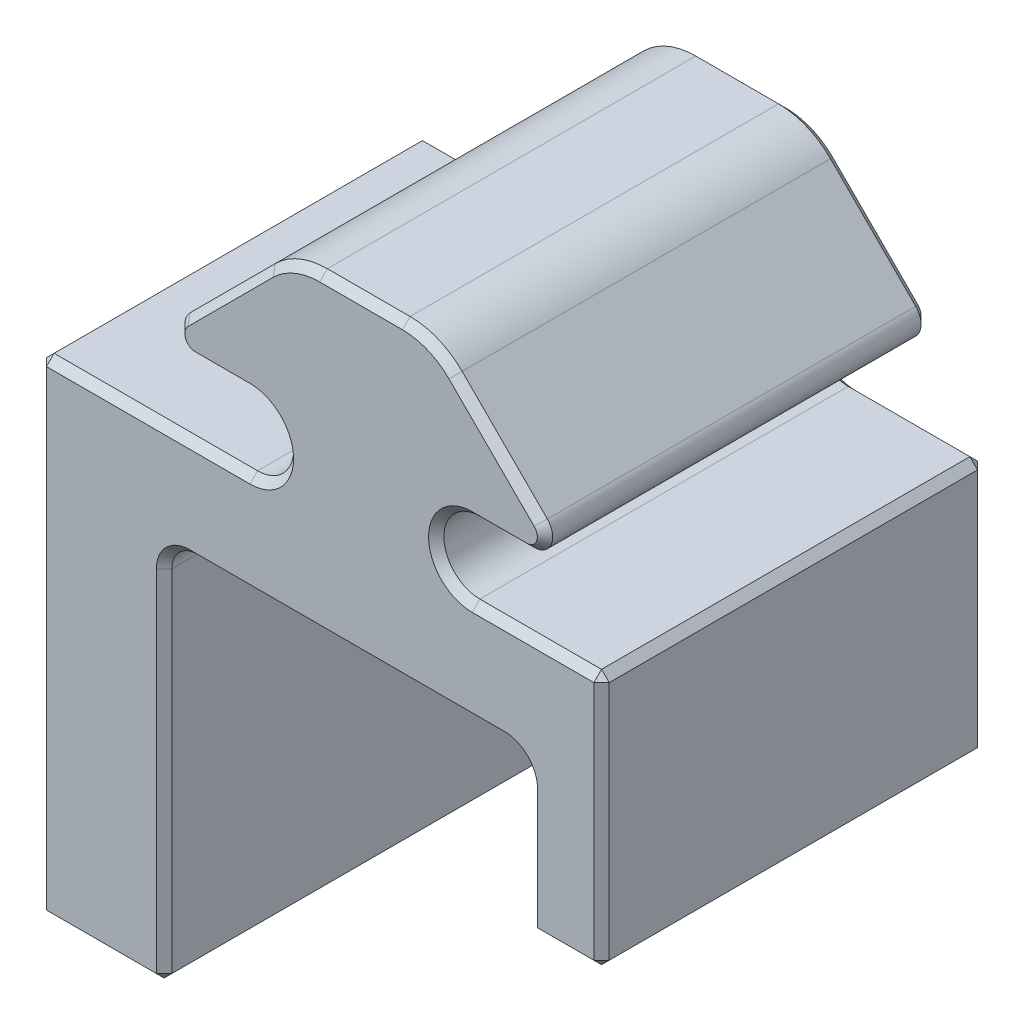
SolidWorks part; units mm, degrees
ref_plane "Front Plane" through (0, 0, 0) normal (0, 0, 1) x (1, 0, 0)
ref_plane "Top Plane" through (0, 0, 0) normal (0, 1, 0) x (1, 0, 0)
ref_plane "Right Plane" through (0, 0, 0) normal (1, 0, 0) x (0, 0, -1)
sketch "Sketch1" plane through (0, 0, 0) normal (0, 0, 1) x (1, 0, 0)
  line L0 (-5.3171, -3.1021) -> (-5.3171, -5.1021) construction
  line L1 (-5.3171, -5.1021) -> (5.3171, -5.1021) construction
  line L2 (5.3171, -5.1021) -> (5.3171, -3.1021) construction
  line L13 (-5.3171, -3.1021) -> (-4.3434, -3.1021) construction
  line L14 (-4.3434, -0.8923) -> (-6.4748, -0.8923) construction
  line L15 (-7.1932, 0.8421) -> (-3.8632, 4.1722) construction
  line L16 (-1.6181, 5.1021) -> (1.6181, 5.1021) construction
  line L17 (3.8632, 4.1722) -> (7.1932, 0.8421) construction
  line L18 (6.4748, -0.8923) -> (4.3434, -0.8923) construction
  line L19 (4.3434, -3.1021) -> (5.3171, -3.1021) construction
  line L20 (-5.0171, -3.4021) -> (-5.0171, -4.8021) construction
  line L21 (-5.0171, -4.8021) -> (5.0171, -4.8021) construction
  line L22 (5.0171, -4.8021) -> (5.0171, -3.4021) construction
  line L23 (4.3434, -3.4021) -> (5.0171, -3.4021)
  line L24 (6.4748, -0.5923) -> (4.3434, -0.5923)
  line L25 (3.651, 3.96) -> (6.9811, 0.63)
  line L26 (-1.6181, 4.8021) -> (1.6181, 4.8021)
  line L27 (-6.9811, 0.63) -> (-3.651, 3.96)
  line L28 (-4.3434, -0.5923) -> (-6.4748, -0.5923)
  line L29 (-5.0171, -3.4021) -> (-4.3434, -3.4021)
  line L30 (-5.0171, -3.4021) -> (-12.6, -3.4021)
  line L31 (-12.6, -3.4021) -> (-12.6, -7.4021)
  line L32 (-12.6, -7.4021) -> (9.4, -7.4021)
  line L33 (9.4, -7.4021) -> (9.4, -3.4021)
  line L34 (9.4, -3.4021) -> (5.0171, -3.4021)
  arc A6 (-4.3434, -3.1021) -> (-4.3434, -0.8923) centre (-4.3434, -1.9972) ccw construction
  arc A7 (-7.1932, 0.8421) -> (-6.4748, -0.8923) centre (-6.4748, 0.1237) ccw construction
  arc A8 (-1.6181, 5.1021) -> (-3.8632, 4.1722) centre (-1.6181, 1.9271) ccw construction
  arc A9 (3.8632, 4.1722) -> (1.6181, 5.1021) centre (1.6181, 1.9271) ccw construction
  arc A10 (6.4748, -0.8923) -> (7.1932, 0.8421) centre (6.4748, 0.1237) ccw construction
  arc A11 (4.3434, -0.8923) -> (4.3434, -3.1021) centre (4.3434, -1.9972) ccw construction
  arc A12 (4.3434, -0.5923) -> (4.3434, -3.4021) centre (4.3434, -1.9972) ccw
  arc A13 (6.4748, -0.5923) -> (6.9811, 0.63) centre (6.4748, 0.1237) ccw
  arc A14 (3.651, 3.96) -> (1.6181, 4.8021) centre (1.6181, 1.9271) ccw
  arc A15 (-1.6181, 4.8021) -> (-3.651, 3.96) centre (-1.6181, 1.9271) ccw
  arc A16 (-6.9811, 0.63) -> (-6.4748, -0.5923) centre (-6.4748, 0.1237) ccw
  arc A17 (-4.3434, -3.4021) -> (-4.3434, -0.5923) centre (-4.3434, -1.9972) ccw
  dimension "D1" = 0.3
  dimension "D2" = 4
  dimension "D3" = 12.6
  dimension "D4" = 22
extrude "Boss-Extrude1" add sketch "Sketch1" along normal blind 15
sketch "Sketch2" plane through (0, -7.4021, 0) normal (0, -1, 0) x (1, 0, 0)
  line L0 (-12.6, 15) -> (9.4, 15) construction
  line L1 (-12.6, 0) -> (-7.7, 0)
  line L2 (-12.6, 0) -> (-12.6, 15)
  line L3 (-12.6, 15) -> (-7.7, 15)
  line L4 (-7.7, 0) -> (-7.7, 15)
  dimension "D1" = 4.9
extrude "Boss-Extrude2" add sketch "Sketch2" along normal blind 15
sketch "Sketch3" plane through (0, -7.4021, 0) normal (0, -1, 0) x (1, 0, 0)
  line L0 (-7.7, 0) -> (9.4, 0) construction
  line L1 (9.4, 15) -> (6.6, 15)
  line L2 (9.4, 15) -> (9.4, 0)
  line L3 (9.4, 0) -> (6.6, 0)
  line L4 (6.6, 15) -> (6.6, 0)
  line L5 (-12.6, 15) -> (-12.6, 0) construction
  dimension "D1" = 19.2
extrude "Boss-Extrude3" add sketch "Sketch3" along normal blind 6
fillet "Fillet1" radius 1 2 edges at (-7.7, -7.4021, 7.5) (6.6, -7.4021, 7.5)
chamfer "Chamfer1" distance 0.3 angle 45 50 edges at (-10.15, -22.4021, 0) (-7.7, -15.4021, 0) (-0.55, -7.4021, 0) (6.6, -10.9021, 0) (8, -13.4021, 0) (9.4, -8.4021, 0) (6.8717, -3.4021, 0) (2.9385, -1.9972, 0) (5.4091, -0.5923, 0) (7.1363, -0.1503, 0) (5.3161, 2.295, 0) (2.7183, 4.5833, 0) (0, 4.8021, 0) (-2.7183, 4.5833, 0) (-5.3161, 2.295, 0) (-7.1363, -0.1503, 0) (-5.4091, -0.5923, 0) (-2.9385, -1.9972, 0) (-8.4717, -3.4021, 0) (-12.6, -12.9021, 0) (-2.9385, -1.9972, 15) (-5.4091, -0.5923, 15) (-7.1363, -0.1503, 15) (-5.3161, 2.295, 15) (-2.7183, 4.5833, 15) (0, 4.8021, 15) (2.7183, 4.5833, 15) (5.3161, 2.295, 15) (7.1363, -0.1503, 15) (5.4091, -0.5923, 15) (2.9385, -1.9972, 15) (6.8717, -3.4021, 15) (9.4, -8.4021, 15) (8, -13.4021, 15) (6.6, -10.9021, 15) (-0.55, -7.4021, 15) (-7.7, -15.4021, 15) (-10.15, -22.4021, 15) (-12.6, -12.9021, 15) (-8.4717, -3.4021, 15) (-12.6, -22.4021, 7.5) (-7.7, -22.4021, 7.5) (6.6, -13.4021, 7.5) (9.4, -13.4021, 7.5) (9.4, -3.4021, 7.5) (-12.6, -3.4021, 7.5) (-7.4071, -7.695, 0) (6.3071, -7.695, 0) (-7.4071, -7.695, 15) (6.3071, -7.695, 15)
